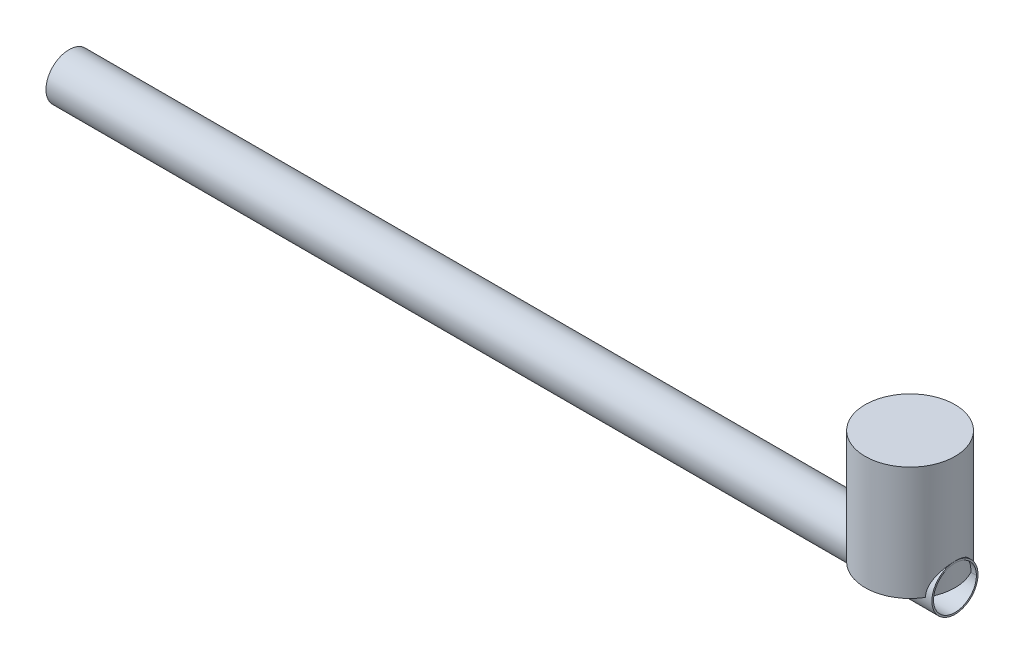
SolidWorks part; units mm, degrees
ref_plane "Front Plane" through (0, 0, 0) normal (0, 0, 1) x (1, 0, 0)
ref_plane "Top Plane" through (0, 0, 0) normal (0, 1, 0) x (1, 0, 0)
ref_plane "Right Plane" through (0, 0, 0) normal (1, 0, 0) x (0, 0, -1)
sketch "Sketch1" plane through (0, 0, 0) normal (1, 0, 0) x (0, 0, -1)
  circle A0 centre (0, 0) radius 12.7
  circle A1 centre (0, 0) radius 11.811
extrude "Boss-Extrude1" add sketch "Sketch1" along normal blind 488.31
sketch "Sketch2" plane through (0, 0, 0) normal (0, 1, 0) x (1, 0, 0)
  circle A0 centre (463.5708, 0) radius 24.7392
extrude "Boss-Extrude2" add sketch "Sketch2" along normal blind 62.7
